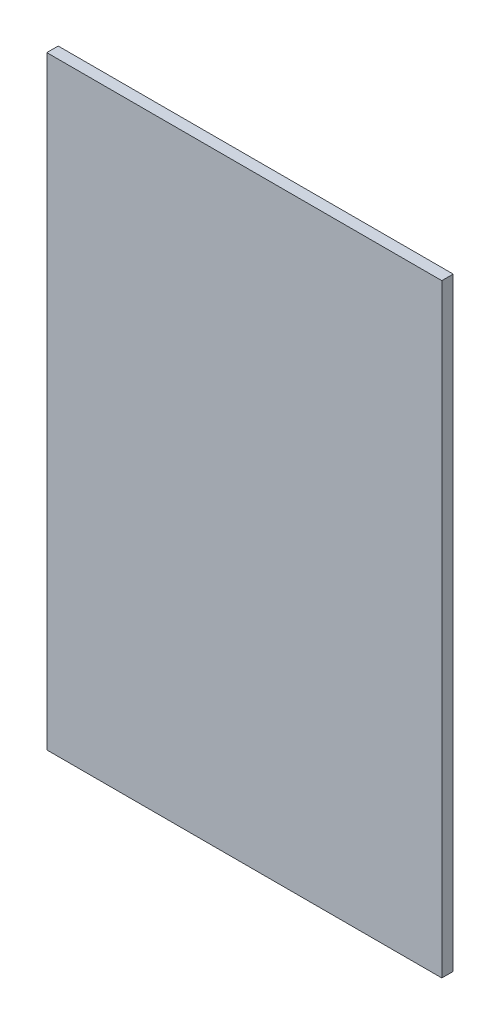
SolidWorks part; units mm, degrees
ref_plane "Plan de face" through (0, 0, 0) normal (0, 0, 1) x (1, 0, 0)
ref_plane "Plan de dessus" through (0, 0, 0) normal (0, 1, 0) x (1, 0, 0)
ref_plane "Plan de droite" through (0, 0, 0) normal (1, 0, 0) x (0, 0, -1)
sketch "Esquisse1" plane through (0, 0, 0) normal (0, 0, 1) x (1, 0, 0)
  line L1 (-38.0708, 42.0538) -> (169.9292, 42.0538)
  line L2 (-38.0708, 42.0538) -> (-38.0708, -275.9462)
  line L3 (-38.0708, -275.9462) -> (169.9292, -275.9462)
  line L4 (169.9292, 42.0538) -> (169.9292, -275.9462)
  dimension "D1" = 318
  dimension "D2" = 208
extrude "Boss.-Extru.1" add sketch "Esquisse1" along normal blind 6
